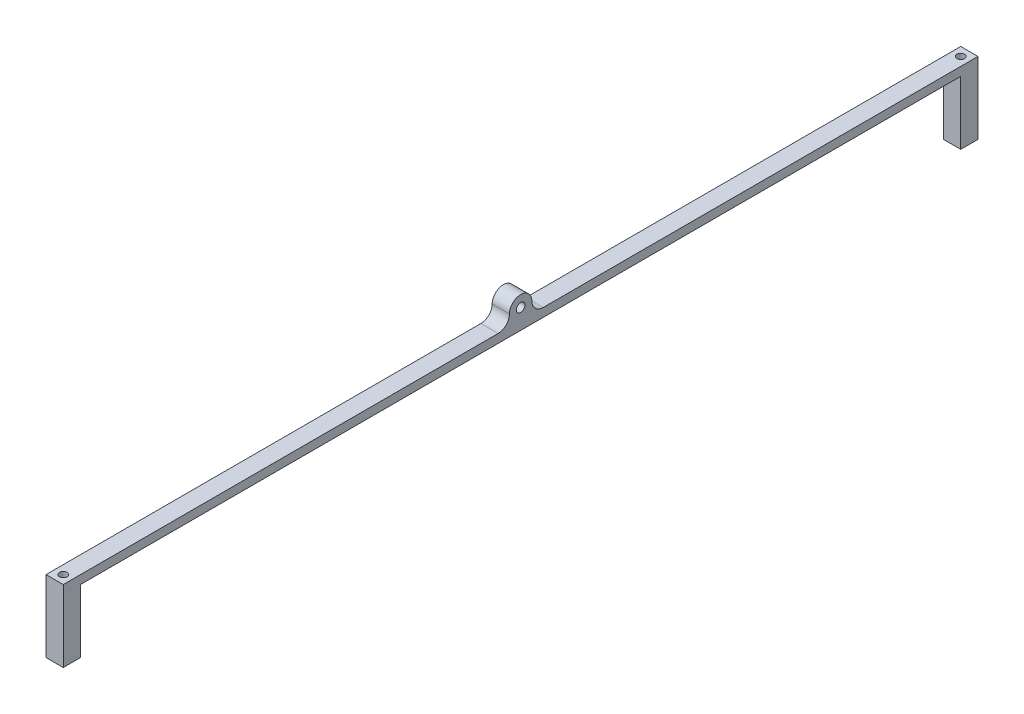
SolidWorks part; units mm, degrees
ref_plane "Спереди" through (0, 0, 0) normal (0, 0, 1) x (1, 0, 0)
ref_plane "Сверху" through (0, 0, 0) normal (0, 1, 0) x (1, 0, 0)
ref_plane "Справа" through (0, 0, 0) normal (1, 0, 0) x (0, 0, -1)
other "Configuration Table"
sketch "Эскиз1" plane through (0, 0, 0) normal (0, 1, 0) x (1, 0, 0)
  line L1 (0, 530) -> (10, 530)
  line L2 (0, 530) -> (0, 0)
  line L3 (0, 0) -> (10, 0)
  line L4 (10, 530) -> (10, 0)
  line L5 (592.3, 530) -> (592.3, 0) construction
  line L7 (0, 520) -> (10, 530) construction
  line L10 (0, 520) -> (10, 520) construction
  line L14 (0, 10) -> (10, 10) construction
  line L16 (0, 530) -> (10, 520) construction
  line L17 (0, 10) -> (10, 0) construction
  line L18 (10, 10) -> (0, 0) construction
  circle A0 centre (5, 525) radius 2.25
  circle A1 centre (5, 5) radius 2.25
  dimension "D5" = 4.5
  dimension "D6" = 4.5
  dimension "D2" = 10
  dimension "D3" = 10
  dimension "D4" = 10
extrude "Бобышка-Вытянуть1" add sketch "Эскиз1" along normal blind 5
sketch "Эскиз2" plane through (0, 0, 0) normal (1, 0, 0) x (0, 0, -1)
  line L0 (258.5, 11.5) -> (271.5, 11.5) construction
  line L1 (252, 5) -> (278, 5)
  line L2 (0, 5) -> (530, 5) construction
  arc A0 (271.5, 11.5) -> (258.5, 11.5) centre (265, 11.5) ccw
  arc A2 (252, 5) -> (258.5, 11.5) centre (252, 11.5) ccw
  arc A3 (271.5, 11.5) -> (278, 5) centre (278, 11.5) ccw
  circle A4 centre (265, 11.5) radius 2.5
  point P1 (265, 5)
  point P5 (265, 5)
  point P6 (271.5, 11.5)
  point P7 (258.5, 11.5)
  dimension "D1" = 13
  dimension "D2" = 13
  dimension "D3" = 13
  dimension "D4" = 5
extrude "Бобышка-Вытянуть2" add sketch "Эскиз2" along normal blind 10
sketch "Эскиз3" plane through (0, 0, 0) normal (0, -1, 0) x (1, 0, 0)
  line L0 (10, 0) -> (10, -530) construction
  line L1 (0, 0) -> (10, 0)
  line L2 (0, 0) -> (0, -10)
  line L3 (0, -10) -> (10, -10)
  line L4 (10, 0) -> (10, -10)
  line L6 (0, -530) -> (10, -530)
  line L7 (0, -530) -> (0, -520)
  line L8 (0, -520) -> (10, -520)
  line L9 (10, -530) -> (10, -520)
  circle A526 centre (5, -525) radius 2.25
  circle A527 centre (5, -525) radius 2.25
  circle A529 centre (5, -5) radius 2.25
  circle A530 centre (5, -5) radius 2.25
  dimension "D1" = 10
  dimension "D2" = 10
  dimension "D3" = 0
  dimension "D4" = 0
extrude "Бобышка-Вытянуть3" add sketch "Эскиз3" along normal up to surface (36.65 mm away)
